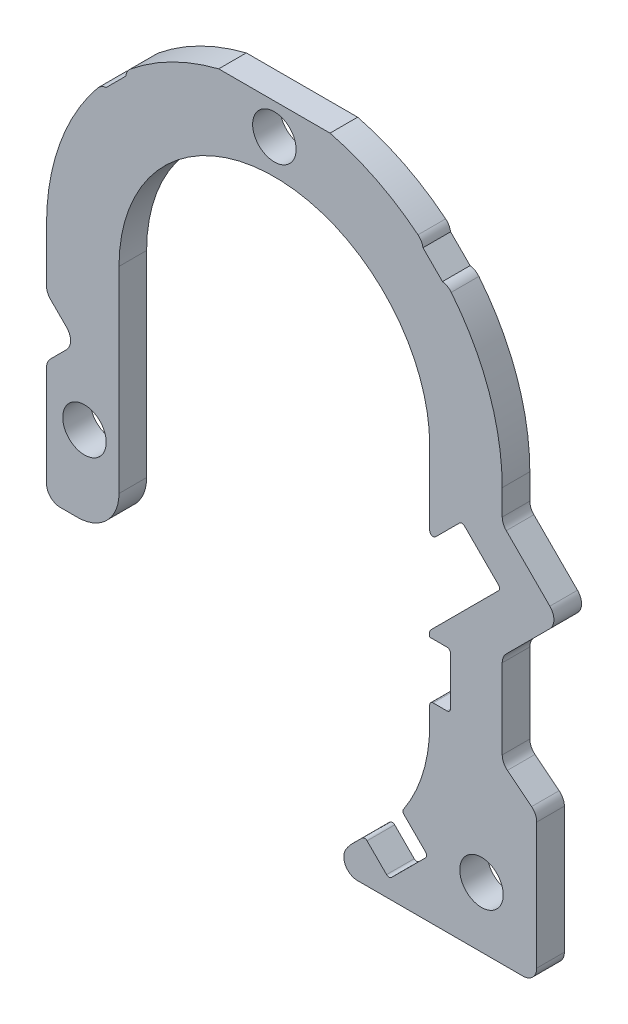
SolidWorks part; units mm, degrees
material "Acrylique (impact moyen-haut)"
ref_plane "Plan de face" through (0, 0, 0) normal (0, 0, 1) x (1, 0, 0)
ref_plane "Plan de dessus" through (0, 0, 0) normal (0, 1, 0) x (1, 0, 0)
ref_plane "Plan de droite" through (0, 0, 0) normal (1, 0, 0) x (0, 0, -1)
sketch "Esquisse5" plane through (0, 0, 0) normal (0, 0, 1) x (1, 0, 0)
  line L0 (18.9052, -48.2483) -> (13.2483, -53.9052) construction
  line L1 (18.9052, -48.2483) -> (21.9104, -51.2536)
  line L2 (13.2483, -53.9052) -> (16.2536, -56.9104)
  line L3 (21.9104, -51.2536) -> (20.5881, -52.5758) construction
  line L4 (17.3284, -46.6715) -> (11.6715, -52.3284)
  line L5 (18.5517, -47.8948) -> (12.8948, -53.5517) construction
  line L6 (21.9104, -51.2536) -> (22.264, -51.6071)
  line L7 (22.264, -51.6071) -> (16.6071, -57.264)
  line L8 (16.6071, -57.264) -> (16.2536, -56.9104)
  line L9 (20.5881, -52.5758) -> (17.5758, -55.5881) construction
  line L10 (17.5758, -55.5881) -> (16.2536, -56.9104) construction
  line L11 (20.25, -32) -> (18.52, -32)
  line L12 (15.7232, -50.7232) -> (16.0768, -51.0768) construction
  line L13 (15.9, -50.9) -> (0, -50.9) construction
  line L14 (0, -50.9) -> (0, 0) construction
  line L15 (12.8948, -53.5517) -> (13.2483, -53.9052)
  line L16 (18.5517, -47.8948) -> (18.9052, -48.2483)
  line L17 (20.25, -24) -> (20.75, -24)
  line L18 (20.75, -24) -> (25, -24)
  line L19 (25, -24) -> (25.5, -24)
  line L20 (25.5, -24) -> (25.5, -32)
  line L21 (25.5, -32) -> (25, -32)
  line L22 (25, -32) -> (20.75, -32)
  line L23 (20.75, -32) -> (20.25, -32)
  line L25 (20.25, -28) -> (20.75, -28) construction
  line L26 (16.0768, -51.0768) -> (16.9708, -51.9708) construction
  line L27 (16.9708, -51.9708) -> (18.0562, -53.0562) construction
  line L28 (20.75, -28) -> (22.0144, -28) construction
  line L29 (22.0144, -28) -> (23.5494, -28) construction
  line L30 (18.5517, -47.8948) -> (17.3284, -46.6715)
  line L31 (12.8948, -53.5517) -> (11.6715, -52.3284)
  line L32 (20.25, -28) -> (18.52, -28) construction
  line L33 (18.52, -32) -> (18.52, -24)
  line L34 (18.52, -24) -> (20.25, -24)
  point P14 (0, 0)
  point P31 (20.5, -28)
  dimension "D1" = 4.25
  dimension "D2" = 8
  dimension "D3" = 2.23
  dimension "D4" = 1.73
  dimension "D5" = 0.5
  dimension "D6" = 4.26
  dimension "D7" = 1.87
  dimension "D8" = 50.9
  dimension "D9" = 15.9
  dimension "D10" = 45
  dimension "D11" = 20.5
  dimension "D12" = 28
  dimension "D13" = 1.2644
  dimension "D14" = 1.535
sketch "Esquisse1" plane through (0, 0, 0) normal (0, 0, 1) x (1, 0, 0)
  line L0 (-22.5, 0) -> (22.5, 0) construction
  line L1 (-22.9365, 22.9365) -> (0, 0) construction
  line L2 (0, 0) -> (22.9365, 22.9365) construction
  line L3 (-22.9365, 22.9365) -> (22.9365, 22.9365) construction
  line L4 (-21.5223, 24.3507) -> (-21.5223, 25.0158)
  line L5 (-24.3507, 21.5223) -> (-21.5223, 24.3507)
  line L6 (21.5223, 24.3507) -> (24.3507, 21.5223)
  line L7 (21.5223, 25.0158) -> (21.5223, 24.3507)
  line L8 (24.3507, 21.5223) -> (25.0158, 21.5223)
  line L9 (-24.3507, 21.5223) -> (-25.0158, 21.5223)
  line L10 (0, 0) -> (0, -34.9802) construction
  line L11 (22.5, 0) -> (22.5, -34.9802)
  line L12 (15.9, -50.9) -> (0, -34.9802) construction
  line L13 (15.9, -50.9) -> (11.2756, -55.5187)
  line L14 (-22.5, 0) -> (-22.5, -28.4809)
  line L15 (-33, -34.4809) -> (-28.5, -34.4809)
  line L16 (15.5156, -59.764) -> (10.6249, -56.2881) construction
  line L17 (33, -34.4809) -> (33, 0)
  line L25 (-33, -34.4809) -> (-33, 0)
  line L26 (9.5156, -59.764) -> (38, -59.764)
  line L28 (-8.0623, 32) -> (8.0623, 32)
  line L29 (33, -34.4809) -> (38, -38.4809)
  line L30 (38, -38.4809) -> (38, -59.764)
  line L31 (-28.5, -34.4809) -> (33, -34.4809) construction
  line L32 (-23.6094, -31.9568) -> (-28.5, -28.4809) construction
  line L33 (10.6249, -56.2881) -> (-23.6094, -31.9568) construction
  line L36 (0, 33) -> (0, 32) construction
  arc A0 (22.5, 0) -> (-22.5, 0) centre (0, 0) ccw
  arc A1 (-21.5223, 25.0158) -> (-8.0623, 32) centre (0, 0) cw
  arc A2 (25.0158, 21.5223) -> (33, 0) centre (0, 0) cw
  arc A3 (-25.0158, 21.5223) -> (-33, 0) centre (0, 0) ccw
  arc A4 (22.5, -34.9802) -> (15.9, -50.9) centre (0, -34.9802) cw
  arc A5 (-22.5, -28.4809) -> (-28.5, -34.4809) centre (-28.5, -28.4809) cw
  circle A6 centre (0, -34.9802) radius 20 construction
  arc A7 (22.5, 0) -> (-22.5, 0) centre (0, 0) cw construction
  arc A9 (11.2756, -55.5187) -> (9.5156, -59.764) centre (15.5156, -59.764) ccw
  arc A11 (-8.0623, 32) -> (8.0623, 32) centre (0, 0) cw construction
  arc A12 (8.0623, 32) -> (21.5223, 25.0158) centre (0, 0) cw
  dimension "D1" = 22.5
  dimension "D6" = 10.5
  dimension "D7" = 1
  dimension "D8" = 2.5
  dimension "D9" = 42
  dimension "D10" = 6
  dimension "D11" = 40
  dimension "D12" = 45.873
  dimension "D2" = 4
  dimension "D3" = 0.6651
  dimension "D4" = 90
  dimension "D5" = 22.9365
  dimension "D14" = 5
  dimension "D15" = 4
extrude "corps" add sketch "Esquisse1" along normal blind 4
hole_wizard "Diamètre du perçage Ø6.2 (6.3)1" positions "Esquisse2" profile "Esquisse3" hole size "Ø6.2" standard "Ansi Metric" end condition through all
sketch "Esquisse2" plane through (0, 0, 4) normal (0, 0, 1) x (1, 0, 0)
  line L0 (-27.5, -23) -> (0, -23) construction
  line L1 (0, -23) -> (0, 0) construction
  line L3 (0, 0) -> (0, 27.5) construction
  line L5 (0, -23) -> (0, -51) construction
  line L6 (0, -51) -> (30, -51) construction
  point P0 (0, 27.5)
  point P2 (30, -51)
  point P4 (-27.5, -23)
  dimension "D4" = 30
  dimension "D1" = 27.5
  dimension "D2" = 23
  dimension "D3" = 28
sketch "Esquisse3" plane through (0, 27.5, 4) normal (1, 0, 0) x (0, -1, 0)
  line L0 (0, 0) -> (0, 4)
  line L1 (0, 4) -> (3.15, 4)
  line L2 (3.15, 4) -> (3.15, 0)
  line L5 (3.15, 0) -> (0, 0)
  line L11 (0, -6.35) -> (0, 107.95) construction
  dimension "Diamètre du perçage jusqu'au prochain" = 6.3
  dimension "Profondeur du perçage jusqu'au prochain" = 4
sketch "Esquisse4" plane through (0, 0, 0) normal (0, 0, 1) x (1, 0, 0)
  line L0 (0, 0) -> (0, -34.9802) construction
  line L1 (0, -34.3431) -> (24.626, -9.7172)
  line L2 (0, -34.3431) -> (0, -45.6569)
  line L3 (0, -45.6569) -> (30.2828, -15.374)
  line L4 (27.1716, -7.1716) -> (32.8284, -12.8284)
  line L5 (-75.9397, -31.7976) -> (-42.8284, 1.3137)
  line L6 (-42.8284, 1.3137) -> (-28.6863, -12.8284)
  line L7 (24.626, -9.7172) -> (30.2828, -15.374) construction
  line L8 (-61.7976, -45.9397) -> (-28.6863, -12.8284)
  line L9 (22.5, 0) -> (22.5, -34.9802) construction
  line L10 (30.2828, -15.374) -> (32.8284, -12.8284)
  line L11 (24.626, -9.7172) -> (27.1716, -7.1716)
  line L12 (-67.4544, -31.7976) -> (-61.7976, -37.4544) construction
  line L13 (-67.4544, -31.7976) -> (-42.8284, -7.1716) construction
  line L14 (-61.7976, -37.4544) -> (-37.1716, -12.8284) construction
  line L15 (-42.8284, -7.1716) -> (-37.1716, -12.8284) construction
  line L16 (-40, -10) -> (30, -10) construction
  line L17 (-75.9397, -31.7976) -> (-61.7976, -45.9397)
  line L18 (31.4142, -2.9289) -> (41.3137, -12.8284)
  line L19 (34.5255, -19.6167) -> (41.3137, -12.8284)
  line L21 (31.4142, -2.9289) -> (24.626, -9.7172)
  line L22 (24.626, -9.7172) -> (27.4544, -26.6877)
  line L23 (27.4544, -26.6877) -> (34.5255, -19.6167)
  line L24 (27.4544, -12.5456) -> (27.4544, -26.6877) construction
  line L25 (27.4544, -12.5456) -> (29.2929, -10.7071) construction
  line L26 (26.8887, -7.4544) -> (32.5456, -13.1113) construction
  point P10 (27.4544, -12.5456)
  point P11 (30, -10)
  point P28 (26.882, -7.3947)
  dimension "D2" = 4.9544
  dimension "D3" = 8
  dimension "D4" = 45
  dimension "D5" = 10
  dimension "D6" = 30
  dimension "D7" = 70
  dimension "D8" = 6
  dimension "D10" = 2.6
  dimension "D11" = 3.2
  dimension "D12" = 0.4
  dimension "D9" = 6
extrude "renfort_cavite_IR" add sketch "Esquisse4" along normal through all contours L19 L18 L21 L22 L23
extrude "cavite_IR" cut sketch "Esquisse4<4>" along normal through all contours L8 L6 L5 L17 | L3 L10 L4 L11 L1 L2
sketch "Esquisse4<4>" plane through (0, 0, 0) normal (0, 0, 1) x (1, 0, 0) same geometry as "Esquisse4"
extrude "cavite_switch" cut sketch "Esquisse5" along normal through all
fillet "Congé1" radius 2 15 edges at (-25.0158, 21.5223, 2) (-21.5223, 25.0158, 2) (25.0158, 21.5223, 2) (21.5223, 25.0158, 2) (33, -4.5147, 2) (41.3137, -12.8284, 2) (33, -21.1421, 2) (33, -34.4809, 2) (38, -38.4809, 2) (38, -59.764, 2) (9.5156, -59.764, 2) (-33, -34.4809, 2) (-33, -17.1421, 2) (-33, -8.5147, 2) (-28.6863, -12.8284, 2)
fillet "Congé2" radius 0.5 11 edges at (16.6071, -57.264, 2) (13.0698, -53.7267, 2) (22.264, -51.6071, 2) (18.4768, -47.8199, 2) (22.5, -32, 2) (25.5, -32, 2) (25.5, -24, 2) (22.5, -11.8431, 2) (27.1716, -7.1716, 2) (32.8284, -12.8284, 2) (22.5, -23.1569, 2)
